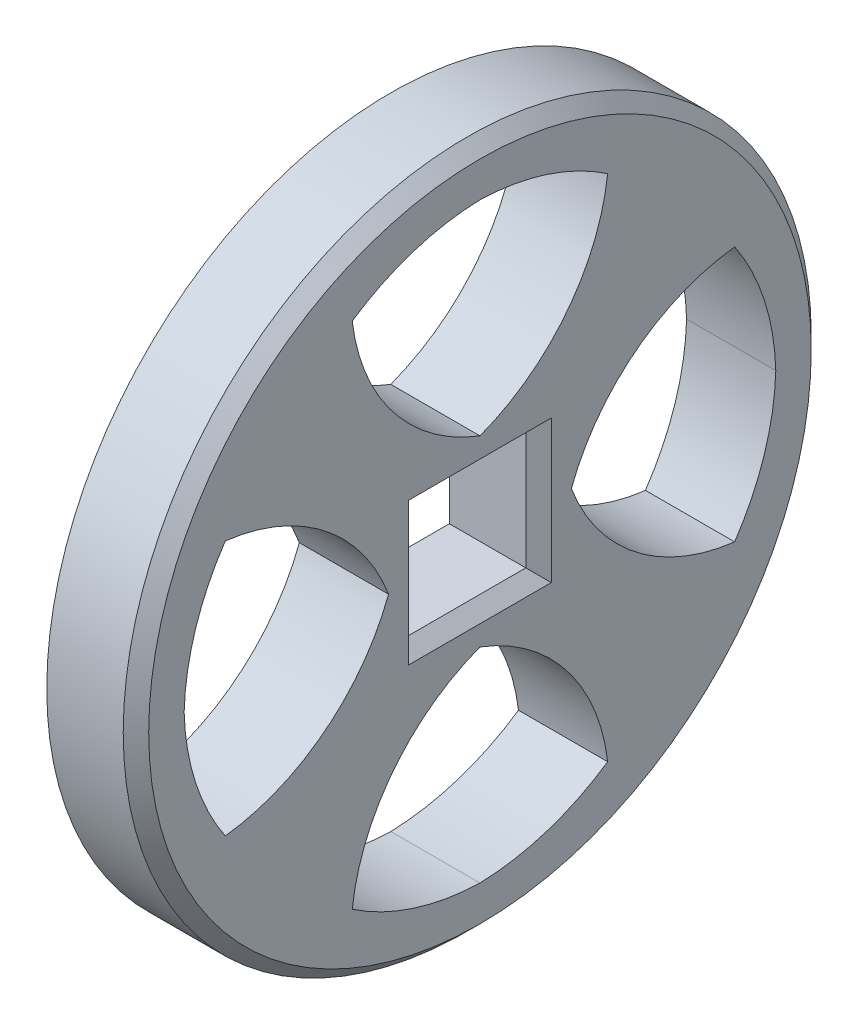
SolidWorks part; units mm, degrees
ref_plane "Front Plane" through (0, 0, 0) normal (0, 0, 1) x (1, 0, 0)
ref_plane "Top Plane" through (0, 0, 0) normal (0, 1, 0) x (1, 0, 0)
ref_plane "Right Plane" through (0, 0, 0) normal (1, 0, 0) x (0, 0, -1)
sketch "Sketch1" plane through (0, 0, 0) normal (1, 0, 0) x (0, 0, -1)
  circle A0 centre (0, 0) radius 13.5
  dimension "D1" = 27
extrude "Boss-Extrude1" add sketch "Sketch1" along normal blind 3.5
sketch "Sketch2" plane through (0, 0, 0) normal (1, 0, 0) x (0, 0, -1)
  line L0 (0, 0) -> (0, 14.8201) construction
  arc A0 (0, 3.5875) -> (-5.0122, 9.994) centre (2.7702, 10.9187) cw
  arc A1 (-5.0122, 9.994) -> (0, 11.6087) centre (0.2591, 2.218) cw
  arc A2 (5.0122, 9.994) -> (0, 11.6087) centre (-0.2591, 2.218) ccw
  arc A3 (0, 3.5875) -> (5.0122, 9.994) centre (-2.7702, 10.9187) ccw
  point P11 (0, 3.5875)
extrude "Cut-Extrude1" cut sketch "Sketch2" along normal up to next
pattern_circular "CirPattern1" count 4 over 360 about axis through (3.5, 0, 0) along (-1, 0, 0) of "Cut-Extrude1" reverse direction yes
sketch "Sketch3" plane through (0, 0, 0) normal (1, 0, 0) x (0, 0, -1)
  line L1 (2.2981, -2.2981) -> (-2.2981, -2.2981)
  line L2 (2.2981, -2.2981) -> (2.2981, 2.2981)
  line L3 (2.2981, 2.2981) -> (-2.2981, 2.2981)
  line L4 (-2.2981, -2.2981) -> (-2.2981, 2.2981)
  line L5 (2.2981, -2.2981) -> (-2.2981, 2.2981) construction
  line L6 (2.2981, 2.2981) -> (-2.2981, -2.2981) construction
  circle A0 centre (0, 0) radius 3.25 construction
  dimension "D1" = 6.5
extrude "Cut-Extrude2" cut sketch "Sketch3" along normal up to next
chamfer "Chamfer1" distance 0.5 angle 45 5 edges at (3.5, 0, 2.2981) (3.5, -2.2981, 0) (3.5, 2.2981, 0) (3.5, 0, -2.2981) (3.5, 0, -13.5)
equation "\"axis_diameter\"=5.66"
equation "\"padding\"=0.5"
